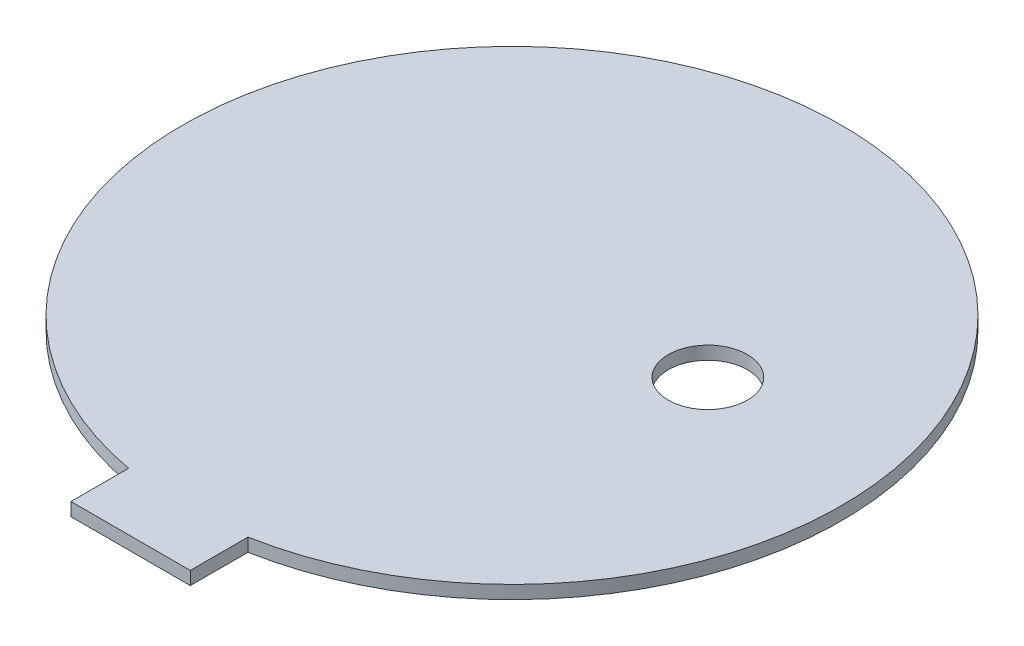
SolidWorks part; units mm, degrees
ref_plane "Front Plane" through (0, 0, 0) normal (0, 0, 1) x (1, 0, 0)
ref_plane "Top Plane" through (0, 0, 0) normal (0, 1, 0) x (1, 0, 0)
ref_plane "Right Plane" through (0, 0, 0) normal (1, 0, 0) x (0, 0, -1)
sketch "Sketch13" plane through (0, 0, 0) normal (0, 1, 0) x (1, 0, 0)
  circle A0 centre (-23, -6.7193) radius 50
extrude "Boss-Extrude6" add sketch "Sketch13" along normal blind 2 contours A0
sketch "Sketch15" plane through (0, 2, 0) normal (0, 1, 0) x (1, 0, 0)
  circle A0 centre (0, 0) radius 6 construction
  circle A1 centre (0, 0) radius 6
extrude "Cut-Extrude5" cut sketch "Sketch15" against normal through all
sketch "Sketch16" plane through (0, 2, 0) normal (0, 1, 0) x (1, 0, 0)
  line L4 (-20, -61.23) -> (-20, -48.33)
  line L5 (-20, -48.33) -> (-25.9, -48.33)
  line L6 (-25.9, -48.33) -> (-25.9, -61.23)
  line L7 (-25.9, -61.23) -> (-20, -61.23)
  line L8 (-20, -61.23) -> (-20, -48.33)
  line L9 (-20, -48.33) -> (-25.9, -48.33)
  line L10 (-25.9, -48.33) -> (-25.9, -61.23)
  line L11 (-25.9, -61.23) -> (-20, -61.23)
  dimension "D1" = 0
extrude "Boss-Extrude7" add sketch "Sketch16" against normal blind 2
sketch "Sketch17" plane through (0, 2, 0) normal (0, 1, 0) x (1, 0, 0)
  line L1 (-25.9, -64.6351) -> (-13.9, -64.6351)
  line L2 (-25.9, -64.6351) -> (-25.9, -56.6351)
  line L3 (-25.9, -56.6351) -> (-13.9, -56.6351)
  line L4 (-13.9, -64.6351) -> (-13.9, -56.6351)
  line L5 (-20, -56.6292) -> (-32, -56.6292)
  line L6 (-20, -56.6292) -> (-20, -64.6351)
  line L7 (-20, -64.6351) -> (-32, -64.6351)
  line L8 (-32, -56.6292) -> (-32, -64.6351)
  arc M3 (-20, -56.6292) -> (-25.9, -56.6351) centre (-23, -6.7193) ccw
  line M4 (-25.9, -56.6351) -> (-25.9, -61.23)
  line M5 (-25.9, -61.23) -> (-20, -61.23)
  line M6 (-20, -61.23) -> (-20, -56.6292)
  dimension "D1" = 12
  dimension "D2" = 8
extrude "Boss-Extrude8" add sketch "Sketch17" against normal blind 2 contours L6 L1 L4 L3 M6 | L6 L2 L1 M5 | L5 L8 L7 L2 M4 M3 region at (-22.95, 2, 62.9326) region at (-28.95, 2, 60.6322) region at (-16.95, 2, 60.6351)
sketch "Sketch18" plane through (0, 2, 0) normal (0, 1, 0) x (1, 0, 0)
  line L0 (-32, -56.6292) -> (-32, -55.9026)
  line L1 (-32, -55.9026) -> (-26, -56.6292)
  line L2 (-26, -56.6292) -> (-32, -56.6292) construction
  line L3 (-26, -56.6292) -> (-32, -56.6292)
  line L4 (-13.9, -56.6351) -> (-13.9, -55.8842)
  line L5 (-13.9, -55.8842) -> (-20, -56.6351)
  line L6 (-20, -56.6351) -> (-13.9, -56.6351)
  arc A0 (-20, -56.6292) -> (-26, -56.6292) centre (-23, -6.7193) ccw construction
extrude "Boss-Extrude9" add sketch "Sketch18" against normal blind 2
